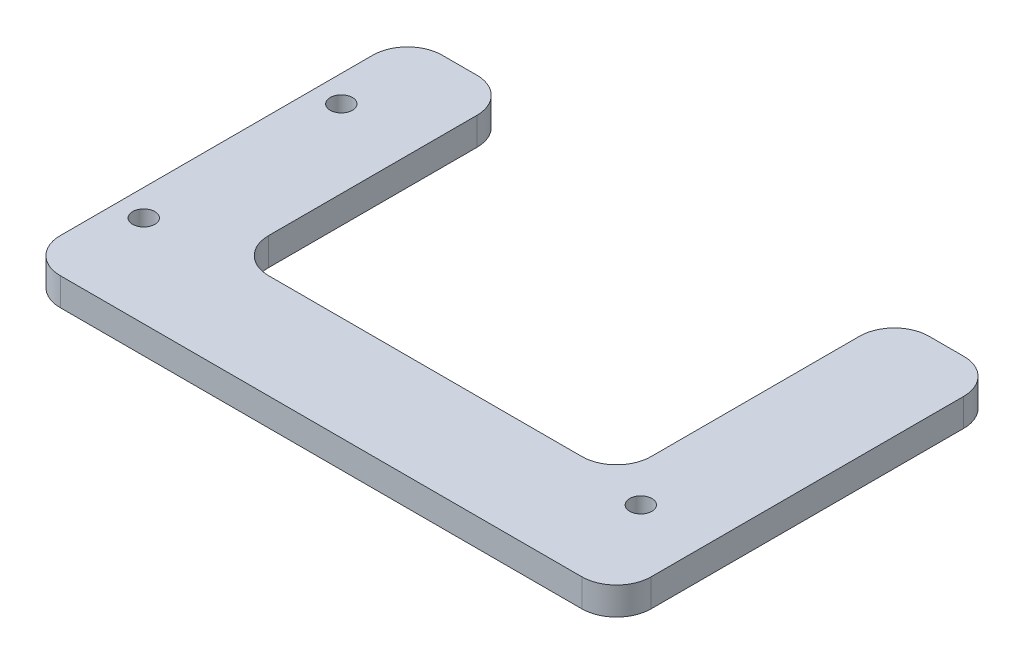
SolidWorks part; units mm, degrees
ref_plane "前视基准面" through (0, 0, 0) normal (0, 0, 1) x (1, 0, 0)
ref_plane "上视基准面" through (0, 0, 0) normal (0, 1, 0) x (1, 0, 0)
ref_plane "右视基准面" through (0, 0, 0) normal (1, 0, 0) x (0, 0, -1)
sketch "草图1" plane through (0, 0, 0) normal (0, 1, 0) x (1, 0, 0)
  line L0 (-38.74, 14.16) -> (-38.74, -14.29) construction
  line L1 (42.55, -27.5) -> (-42.55, -27.5)
  line L2 (42.55, -27.5) -> (42.55, 27.5)
  line L3 (42.55, 27.5) -> (-42.55, 27.5)
  line L4 (-42.55, -27.5) -> (-42.55, 27.5)
  line L5 (42.55, -27.5) -> (-42.55, 27.5) construction
  line L6 (42.55, 27.5) -> (-42.55, -27.5) construction
  line L7 (-38.74, -14.29) -> (32.84, -14.29) construction
  circle A0 centre (-38.74, 14.16) radius 1.6
  circle A1 centre (-38.74, -14.29) radius 1.6
  circle A2 centre (32.84, -14.29) radius 1.6
  point P0 (0, 0)
  dimension "D5" = 3.2
  dimension "D1" = 55
  dimension "D2" = 85.1
  dimension "D3" = 3.81
  dimension "D4" = 9.71
  dimension "D6" = 13.21
  dimension "D7" = 13.34
extrude "凸台-拉伸1" add sketch "草图1" along normal blind 4
sketch "上机架螺钉头占位" plane through (0, 0, 0) normal (0, 1, 0) x (1, 0, 0)
  line L0 (-16, 7.5) -> (16, 7.5) construction
  line L1 (0, 7.5) -> (0, 0) construction
  line L2 (42.55, 27.5) -> (-42.55, 27.5) construction
  line L3 (-16, 7.5) -> (-16, -2.5) construction
  line L4 (-16, -2.5) -> (16, -2.5) construction
  line L5 (16, -2.5) -> (16, 7.5) construction
  circle A0 centre (-16, 7.5) radius 3
  circle A1 centre (16, 7.5) radius 3
  circle A2 centre (-16, -2.5) radius 3
  circle A3 centre (16, -2.5) radius 3
  dimension "D2" = 6
  dimension "D1" = 20
  dimension "D3" = 32
  dimension "D4" = 10
sketch "草图3" plane through (0, 0, 0) normal (0, 1, 0) x (1, 0, 0)
  line L0 (42.55, 27.5) -> (-42.55, 27.5) construction
  line L1 (27.55, -12.5) -> (-27.55, -12.5)
  line L2 (27.55, -12.5) -> (27.55, 27.5)
  line L3 (27.55, 27.5) -> (-27.55, 27.5)
  line L4 (-27.55, -12.5) -> (-27.55, 27.5)
  line L5 (27.55, -12.5) -> (-27.55, 27.5) construction
  line L6 (27.55, 27.5) -> (-27.55, -12.5) construction
  line L7 (0, 7.5) -> (0, 0) construction
  line L8 (42.55, -27.5) -> (42.55, 27.5) construction
  line L9 (-42.55, -27.5) -> (42.55, -27.5) construction
  point P0 (0, 7.5)
  dimension "D1" = 15
  dimension "D2" = 15
extrude "切除-拉伸2" cut sketch "草图3" along normal up to next
fillet "圆角1" radius 5 8 edges at (27.55, 2, 12.5) (27.55, 2, -27.5) (42.55, 2, -27.5) (42.55, 2, 27.5) (-42.55, 2, 27.5) (-27.55, 2, 12.5) (-42.55, 2, -27.5) (-27.55, 2, -27.5)
